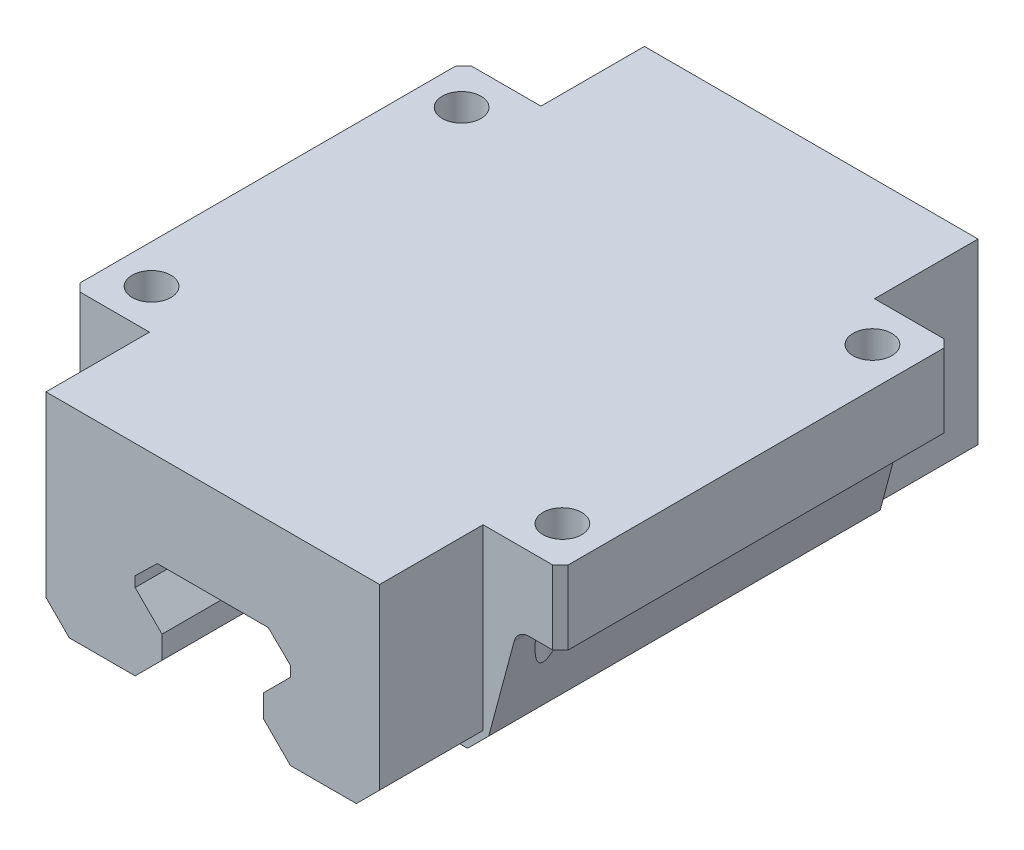
SolidWorks part; units mm, degrees
ref_plane "Front Plane" through (0, 0, 0) normal (0, 0, 1) x (1, 0, 0)
ref_plane "Top Plane" through (0, 0, 0) normal (0, 1, 0) x (1, 0, 0)
ref_plane "Right Plane" through (0, 0, 0) normal (1, 0, 0) x (0, 0, -1)
sketch "Sketch3" plane through (0, 0, 0) normal (0, 0, 1) x (1, 0, 0)
  line L0 (0, 0) -> (0, 18) construction
  line L1 (-10.0182, 0) -> (10.0182, 0)
  line L2 (10.0182, 0) -> (10.0182, 4.0182)
  line L3 (10.0182, 4.0182) -> (6.55, 7.4865)
  line L4 (6.55, 7.4865) -> (6.55, 10.4165)
  line L5 (6.55, 10.4165) -> (10.0182, 13.8847)
  line L6 (10.0182, 13.8847) -> (10.0182, 15.2147)
  line L7 (10.0182, 15.2147) -> (7.16, 18)
  line L8 (7.16, 18) -> (-7.16, 18)
  line L9 (10.0182, 1.0182) -> (9, 0)
  line L10 (-10.0182, 1.0182) -> (-9, 0)
  line L11 (-10.0182, 0) -> (-10.0182, 4.0182)
  line L12 (-10.0182, 4.0182) -> (-6.55, 7.4865)
  line L13 (-6.55, 7.4865) -> (-6.55, 10.4165)
  line L14 (-6.55, 10.4165) -> (-10.0182, 13.8847)
  line L15 (-10.0182, 13.8847) -> (-10.0182, 15.2147)
  line L16 (-10.0182, 15.2147) -> (-7.16, 18)
  line L17 (10.0182, 4.0182) -> (21.5182, 4.0182)
  line L18 (21.5182, 4.0182) -> (25.9345, 20.5)
  line L19 (25.9345, 20.5) -> (31.5, 20.5)
  line L20 (31.5, 20.5) -> (31.5, 30)
  line L21 (31.5, 30) -> (-31.5, 30)
  line L22 (21.5182, 4.0182) -> (21.5182, 30)
  line L23 (-10.0182, 4.0182) -> (-21.5182, 4.0182)
  line L24 (-21.5182, 4.0182) -> (-25.9345, 20.5)
  line L25 (-25.9345, 20.5) -> (-31.5, 20.5)
  line L26 (-21.5182, 4.0182) -> (-21.5182, 30)
  line L27 (-31.5, 20.5) -> (-31.5, 30)
  point P21 (0, 30)
  dimension "D1" = 7.16
  dimension "D2" = 135
  dimension "D3" = 135
  dimension "D4" = 2.93
  dimension "D5" = 1.33
  dimension "D6" = 1.44
  dimension "D7" = 45
  dimension "D8" = 9
  dimension "D9" = 6.55
  dimension "D10" = 3
  dimension "D11" = 18
  dimension "D12" = 31.5
  dimension "D13" = 9.5
  dimension "D14" = 12
  dimension "D15" = 105
  dimension "D16" = 11.5
extrude "Boss-Extrude1" add sketch "Sketch3" along normal blind 38.6 and the other way blind 38.6 contours L26 L23 L12 L13 L14 L15 L16 L8 L7 L6 L5 L4 L3 L17 L22 L21 region at (0, 18.4959, 0)
extrude "Boss-Extrude2" add sketch "Sketch3<4>" along normal blind 25.25 and the other way blind 25.25 contours L27 L25 L24 L26 L21 | L22 L18 L19 L20 L21 region at (-25.5332, 22.4089, 0) region at (25.5332, 22.4089, 0)
sketch "Sketch3<4>" plane through (0, 0, 0) normal (0, 0, 1) x (1, 0, 0) same geometry as "Sketch3"
chamfer "Chamfer1" distance 3 angle 45 4 edges at (-21.5182, 4.0182, 31.925) (21.5182, 4.0182, 31.925) (21.5182, 4.0182, -31.925) (-21.5182, 4.0182, -31.925)
chamfer "Chamfer2" distance 2 angle 45 2 edges at (21.5182, 4.0182, 0) (-21.5182, 4.0182, 0) first distance on face at (17.1432, 4.0182, 0) first distance on face at (-17.1432, 4.0182, 0)
fillet "Fillet1" radius 2 2 edges at (-25.9345, 20.5, 0) (25.9345, 20.5, 0)
sketch "Sketch4" plane through (0, 30, 0) normal (0, 1, 0) x (1, 0, 0)
  line L1 (-26.5, -20) -> (26.5, -20) construction
  line L2 (-26.5, -20) -> (-26.5, 20) construction
  line L3 (-26.5, 20) -> (26.5, 20) construction
  line L4 (26.5, -20) -> (26.5, 20) construction
  line L5 (-26.5, -20) -> (26.5, 20) construction
  line L6 (-26.5, 20) -> (26.5, -20) construction
  point P0 (0, 0)
  dimension "D1" = 53
  dimension "D2" = 40
hole_wizard "M6x1.0 Tapped Hole1" positions "3DSketch1" profile "Sketch6" tap size "M6x1.0" standard "ANSI Metric"
sketch3d "3DSketch1"
  point P0 (-26.5, 30, 20)
  point P3 (-26.5, 30, -20)
  point P6 (26.5, 30, -20)
  point P9 (26.5, 30, 20)
sketch "Sketch6" plane through (-26.5, 30, 20) normal (1, 0, 0) x (0, 0, 1)
  line L0 (0, 0) -> (0, 27.4839)
  line L1 (0, 27.4839) -> (2.5, 25.9818)
  line L2 (2.5, 25.9818) -> (2.5, 0)
  line L5 (2.5, 0) -> (0, 0)
  line L10 (0, 27.4839) -> (-2.5, 25.9818) construction
  line L11 (0, -6.35) -> (0, 107.95) construction
  dimension "Tap Drill Dia." = 5
  dimension "Tap Drill Depth" = 25.9818
  dimension "Drill Angle" = 118
chamfer "Chamfer3" distance 1 angle 45 4 edges at (-31.5, 25.25, 25.25) (31.5, 25.25, 25.25) (31.5, 25.25, -25.25) (-31.5, 25.25, -25.25)
equation "\"D2@Boss-Extrude1\"=3"
